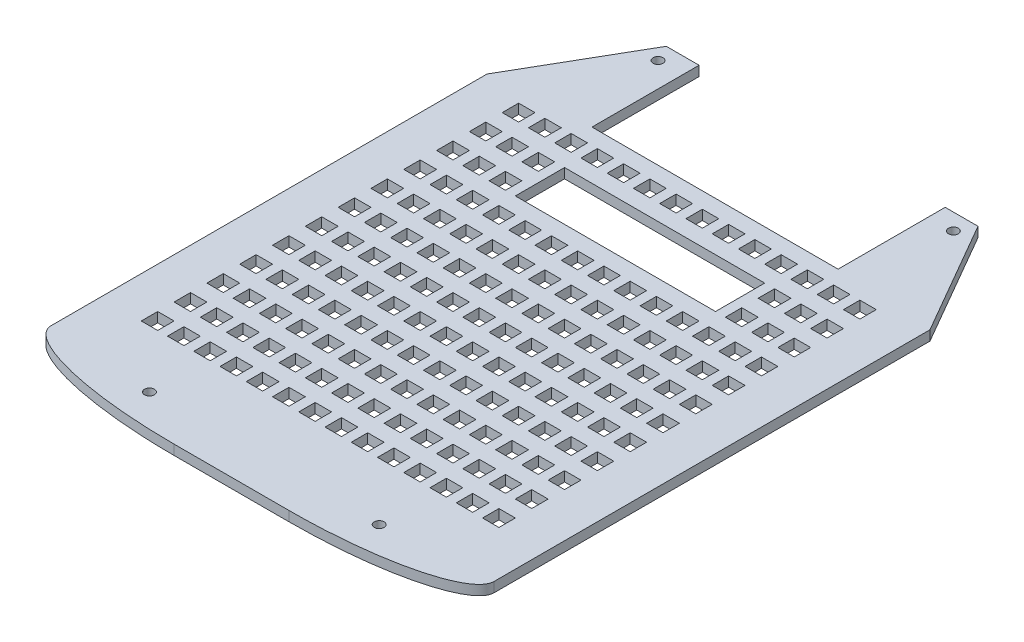
SolidWorks part; units mm, degrees
material "Balsa"
ref_plane "Alzado" through (0, 0, 0) normal (0, 0, 1) x (1, 0, 0)
ref_plane "Planta" through (0, 0, 0) normal (0, 1, 0) x (1, 0, 0)
ref_plane "Vista lateral" through (0, 0, 0) normal (1, 0, 0) x (0, 0, -1)
sketch "Sketch2" plane through (0, 0, 0) normal (0, 1, 0) x (1, 0, 0)
  line L1 (-67.5, 90) -> (67.5, 90)
  line L2 (-67.5, 90) -> (-67.5, -90)
  line L3 (-67.5, -90) -> (67.5, -90)
  line L4 (67.5, 90) -> (67.5, -90)
  line L5 (-67.5, 90) -> (67.5, -90) construction
  line L6 (-67.5, -90) -> (67.5, 90) construction
  point P0 (0, 0)
  dimension "D1" = 135
  dimension "D2" = 180
extrude "Boss-Extrude2" add sketch "Sketch2" along normal blind 3
fillet "Fillet1" radius 12.5 1 edges at (-67.5, 1.5, 90) second distance 50 first distance on face at (-67.5, 1.5, 0)
fillet "Fillet2" radius 12.5 1 edges at (67.5, 1.5, 90) second distance 50 first distance on face at (67.5, 1.5, 0)
chamfer "Chamfer2" distance 20 angle 60 1 edges at (67.5, 1.5, -90) first distance on face at (0, 1.5, -90)
chamfer "Chamfer3" distance 20 angle 60 1 edges at (-67.5, 1.5, -90) first distance on face at (-10, 1.5, -90)
sketch "Sketch3" plane through (0, 3, 0) normal (0, 1, 0) x (1, 0, 0)
  line L0 (0, 90) -> (0, -90) construction
  line L1 (47.5, 90) -> (-47.5, 90) construction
  line L2 (-17.5, -90) -> (17.5, -90) construction
  circle A0 centre (-35, -80) radius 1.5
  circle A1 centre (-45, 85) radius 1.5
  circle A2 centre (35, -80) radius 1.5
  circle A3 centre (45, 85) radius 1.5
  dimension "D1" = 3
  dimension "D3" = 35
  dimension "D2" = 10
  dimension "D4" = 5
  dimension "D5" = 45
extrude "Cut-Extrude1" cut sketch "Sketch3" against normal blind 10
sketch "Sketch4" plane through (0, 3, 0) normal (0, 1, 0) x (1, 0, 0)
  line L1 (-55, 52.5) -> (-50, 52.5)
  line L2 (-55, 52.5) -> (-55, 47.5)
  line L3 (-55, 47.5) -> (-50, 47.5)
  line L4 (-50, 52.5) -> (-50, 47.5)
  line L674 (47.5, 90) -> (-47.5, 90) construction
  line L675 (-67.5, 55.359) -> (-67.5, -77.5) construction
  line L839 (-47, 52.5) -> (-47, 47.5)
  line L840 (-47, 52.5) -> (-42, 52.5)
  line L841 (-42, 52.5) -> (-42, 47.5)
  line L842 (-47, 47.5) -> (-42, 47.5)
  line L843 (-39, 52.5) -> (-39, 47.5)
  line L844 (-39, 52.5) -> (-34, 52.5)
  line L845 (-34, 52.5) -> (-34, 47.5)
  line L846 (-39, 47.5) -> (-34, 47.5)
  line L847 (-31, 52.5) -> (-31, 47.5)
  line L848 (-31, 52.5) -> (-26, 52.5)
  line L849 (-26, 52.5) -> (-26, 47.5)
  line L850 (-31, 47.5) -> (-26, 47.5)
  line L851 (-23, 52.5) -> (-23, 47.5)
  line L852 (-23, 52.5) -> (-18, 52.5)
  line L853 (-18, 52.5) -> (-18, 47.5)
  line L854 (-23, 47.5) -> (-18, 47.5)
  line L855 (-15, 52.5) -> (-15, 47.5)
  line L856 (-15, 52.5) -> (-10, 52.5)
  line L857 (-10, 52.5) -> (-10, 47.5)
  line L858 (-15, 47.5) -> (-10, 47.5)
  line L859 (-7, 52.5) -> (-7, 47.5)
  line L860 (-7, 52.5) -> (-2, 52.5)
  line L861 (-2, 52.5) -> (-2, 47.5)
  line L862 (-7, 47.5) -> (-2, 47.5)
  line L863 (1, 52.5) -> (1, 47.5)
  line L864 (1, 52.5) -> (6, 52.5)
  line L865 (6, 52.5) -> (6, 47.5)
  line L866 (1, 47.5) -> (6, 47.5)
  line L867 (9, 52.5) -> (9, 47.5)
  line L868 (9, 52.5) -> (14, 52.5)
  line L869 (14, 52.5) -> (14, 47.5)
  line L870 (9, 47.5) -> (14, 47.5)
  line L871 (17, 52.5) -> (17, 47.5)
  line L872 (17, 52.5) -> (22, 52.5)
  line L873 (22, 52.5) -> (22, 47.5)
  line L874 (17, 47.5) -> (22, 47.5)
  line L875 (25, 52.5) -> (25, 47.5)
  line L876 (25, 52.5) -> (30, 52.5)
  line L877 (30, 52.5) -> (30, 47.5)
  line L878 (25, 47.5) -> (30, 47.5)
  line L879 (33, 52.5) -> (33, 47.5)
  line L880 (33, 52.5) -> (38, 52.5)
  line L881 (38, 52.5) -> (38, 47.5)
  line L882 (33, 47.5) -> (38, 47.5)
  line L883 (41, 52.5) -> (41, 47.5)
  line L884 (41, 52.5) -> (46, 52.5)
  line L885 (46, 52.5) -> (46, 47.5)
  line L886 (41, 47.5) -> (46, 47.5)
  line L887 (49, 52.5) -> (49, 47.5)
  line L888 (49, 52.5) -> (54, 52.5)
  line L889 (54, 52.5) -> (54, 47.5)
  line L890 (49, 47.5) -> (54, 47.5)
  line L891 (-47, 42.5) -> (-47, 37.5)
  line L892 (-47, 42.5) -> (-42, 42.5)
  line L893 (-42, 42.5) -> (-42, 37.5)
  line L894 (-47, 37.5) -> (-42, 37.5)
  line L895 (-39, 42.5) -> (-39, 37.5)
  line L896 (-39, 42.5) -> (-34, 42.5)
  line L897 (-34, 42.5) -> (-34, 37.5)
  line L898 (-39, 37.5) -> (-34, 37.5)
  line L899 (-31, 42.5) -> (-31, 37.5)
  line L900 (-31, 42.5) -> (-26, 42.5)
  line L901 (-26, 42.5) -> (-26, 37.5)
  line L902 (-31, 37.5) -> (-26, 37.5)
  line L903 (-23, 42.5) -> (-23, 37.5)
  line L904 (-23, 42.5) -> (-18, 42.5)
  line L905 (-18, 42.5) -> (-18, 37.5)
  line L906 (-23, 37.5) -> (-18, 37.5)
  line L907 (-15, 42.5) -> (-15, 37.5)
  line L908 (-15, 42.5) -> (-10, 42.5)
  line L909 (-10, 42.5) -> (-10, 37.5)
  line L910 (-15, 37.5) -> (-10, 37.5)
  line L911 (-7, 42.5) -> (-7, 37.5)
  line L912 (-7, 42.5) -> (-2, 42.5)
  line L913 (-2, 42.5) -> (-2, 37.5)
  line L914 (-7, 37.5) -> (-2, 37.5)
  line L915 (1, 42.5) -> (1, 37.5)
  line L916 (1, 42.5) -> (6, 42.5)
  line L917 (6, 42.5) -> (6, 37.5)
  line L918 (1, 37.5) -> (6, 37.5)
  line L919 (9, 42.5) -> (9, 37.5)
  line L920 (9, 42.5) -> (14, 42.5)
  line L921 (14, 42.5) -> (14, 37.5)
  line L922 (9, 37.5) -> (14, 37.5)
  line L923 (17, 42.5) -> (17, 37.5)
  line L924 (17, 42.5) -> (22, 42.5)
  line L925 (22, 42.5) -> (22, 37.5)
  line L926 (17, 37.5) -> (22, 37.5)
  line L927 (25, 42.5) -> (25, 37.5)
  line L928 (25, 42.5) -> (30, 42.5)
  line L929 (30, 42.5) -> (30, 37.5)
  line L930 (25, 37.5) -> (30, 37.5)
  line L931 (33, 42.5) -> (33, 37.5)
  line L932 (33, 42.5) -> (38, 42.5)
  line L933 (38, 42.5) -> (38, 37.5)
  line L934 (33, 37.5) -> (38, 37.5)
  line L935 (41, 42.5) -> (41, 37.5)
  line L936 (41, 42.5) -> (46, 42.5)
  line L937 (46, 42.5) -> (46, 37.5)
  line L938 (41, 37.5) -> (46, 37.5)
  line L939 (49, 42.5) -> (49, 37.5)
  line L940 (49, 42.5) -> (54, 42.5)
  line L941 (54, 42.5) -> (54, 37.5)
  line L942 (49, 37.5) -> (54, 37.5)
  line L943 (-47, 32.5) -> (-47, 27.5)
  line L944 (-47, 32.5) -> (-42, 32.5)
  line L945 (-42, 32.5) -> (-42, 27.5)
  line L946 (-47, 27.5) -> (-42, 27.5)
  line L947 (-39, 32.5) -> (-39, 27.5)
  line L948 (-39, 32.5) -> (-34, 32.5)
  line L949 (-34, 32.5) -> (-34, 27.5)
  line L950 (-39, 27.5) -> (-34, 27.5)
  line L951 (-31, 32.5) -> (-31, 27.5)
  line L952 (-31, 32.5) -> (-26, 32.5)
  line L953 (-26, 32.5) -> (-26, 27.5)
  line L954 (-31, 27.5) -> (-26, 27.5)
  line L955 (-23, 32.5) -> (-23, 27.5)
  line L956 (-23, 32.5) -> (-18, 32.5)
  line L957 (-18, 32.5) -> (-18, 27.5)
  line L958 (-23, 27.5) -> (-18, 27.5)
  line L959 (-15, 32.5) -> (-15, 27.5)
  line L960 (-15, 32.5) -> (-10, 32.5)
  line L961 (-10, 32.5) -> (-10, 27.5)
  line L962 (-15, 27.5) -> (-10, 27.5)
  line L963 (-7, 32.5) -> (-7, 27.5)
  line L964 (-7, 32.5) -> (-2, 32.5)
  line L965 (-2, 32.5) -> (-2, 27.5)
  line L966 (-7, 27.5) -> (-2, 27.5)
  line L967 (1, 32.5) -> (1, 27.5)
  line L968 (1, 32.5) -> (6, 32.5)
  line L969 (6, 32.5) -> (6, 27.5)
  line L970 (1, 27.5) -> (6, 27.5)
  line L971 (9, 32.5) -> (9, 27.5)
  line L972 (9, 32.5) -> (14, 32.5)
  line L973 (14, 32.5) -> (14, 27.5)
  line L974 (9, 27.5) -> (14, 27.5)
  line L975 (17, 32.5) -> (17, 27.5)
  line L976 (17, 32.5) -> (22, 32.5)
  line L977 (22, 32.5) -> (22, 27.5)
  line L978 (17, 27.5) -> (22, 27.5)
  line L979 (25, 32.5) -> (25, 27.5)
  line L980 (25, 32.5) -> (30, 32.5)
  line L981 (30, 32.5) -> (30, 27.5)
  line L982 (25, 27.5) -> (30, 27.5)
  line L983 (33, 32.5) -> (33, 27.5)
  line L984 (33, 32.5) -> (38, 32.5)
  line L985 (38, 32.5) -> (38, 27.5)
  line L986 (33, 27.5) -> (38, 27.5)
  line L987 (41, 32.5) -> (41, 27.5)
  line L988 (41, 32.5) -> (46, 32.5)
  line L989 (46, 32.5) -> (46, 27.5)
  line L990 (41, 27.5) -> (46, 27.5)
  line L991 (49, 32.5) -> (49, 27.5)
  line L992 (49, 32.5) -> (54, 32.5)
  line L993 (54, 32.5) -> (54, 27.5)
  line L994 (49, 27.5) -> (54, 27.5)
  line L995 (-47, 22.5) -> (-47, 17.5)
  line L996 (-47, 22.5) -> (-42, 22.5)
  line L997 (-42, 22.5) -> (-42, 17.5)
  line L998 (-47, 17.5) -> (-42, 17.5)
  line L999 (-39, 22.5) -> (-39, 17.5)
  line L1000 (-39, 22.5) -> (-34, 22.5)
  line L1001 (-34, 22.5) -> (-34, 17.5)
  line L1002 (-39, 17.5) -> (-34, 17.5)
  line L1003 (-31, 22.5) -> (-31, 17.5)
  line L1004 (-31, 22.5) -> (-26, 22.5)
  line L1005 (-26, 22.5) -> (-26, 17.5)
  line L1006 (-31, 17.5) -> (-26, 17.5)
  line L1007 (-23, 22.5) -> (-23, 17.5)
  line L1008 (-23, 22.5) -> (-18, 22.5)
  line L1009 (-18, 22.5) -> (-18, 17.5)
  line L1010 (-23, 17.5) -> (-18, 17.5)
  line L1011 (-15, 22.5) -> (-15, 17.5)
  line L1012 (-15, 22.5) -> (-10, 22.5)
  line L1013 (-10, 22.5) -> (-10, 17.5)
  line L1014 (-15, 17.5) -> (-10, 17.5)
  line L1015 (-7, 22.5) -> (-7, 17.5)
  line L1016 (-7, 22.5) -> (-2, 22.5)
  line L1017 (-2, 22.5) -> (-2, 17.5)
  line L1018 (-7, 17.5) -> (-2, 17.5)
  line L1019 (1, 22.5) -> (1, 17.5)
  line L1020 (1, 22.5) -> (6, 22.5)
  line L1021 (6, 22.5) -> (6, 17.5)
  line L1022 (1, 17.5) -> (6, 17.5)
  line L1023 (9, 22.5) -> (9, 17.5)
  line L1024 (9, 22.5) -> (14, 22.5)
  line L1025 (14, 22.5) -> (14, 17.5)
  line L1026 (9, 17.5) -> (14, 17.5)
  line L1027 (17, 22.5) -> (17, 17.5)
  line L1028 (17, 22.5) -> (22, 22.5)
  line L1029 (22, 22.5) -> (22, 17.5)
  line L1030 (17, 17.5) -> (22, 17.5)
  line L1031 (25, 22.5) -> (25, 17.5)
  line L1032 (25, 22.5) -> (30, 22.5)
  line L1033 (30, 22.5) -> (30, 17.5)
  line L1034 (25, 17.5) -> (30, 17.5)
  line L1035 (33, 22.5) -> (33, 17.5)
  line L1036 (33, 22.5) -> (38, 22.5)
  line L1037 (38, 22.5) -> (38, 17.5)
  line L1038 (33, 17.5) -> (38, 17.5)
  line L1039 (41, 22.5) -> (41, 17.5)
  line L1040 (41, 22.5) -> (46, 22.5)
  line L1041 (46, 22.5) -> (46, 17.5)
  line L1042 (41, 17.5) -> (46, 17.5)
  line L1043 (49, 22.5) -> (49, 17.5)
  line L1044 (49, 22.5) -> (54, 22.5)
  line L1045 (54, 22.5) -> (54, 17.5)
  line L1046 (49, 17.5) -> (54, 17.5)
  line L1047 (-47, 12.5) -> (-47, 7.5)
  line L1048 (-47, 12.5) -> (-42, 12.5)
  line L1049 (-42, 12.5) -> (-42, 7.5)
  line L1050 (-47, 7.5) -> (-42, 7.5)
  line L1051 (-39, 12.5) -> (-39, 7.5)
  line L1052 (-39, 12.5) -> (-34, 12.5)
  line L1053 (-34, 12.5) -> (-34, 7.5)
  line L1054 (-39, 7.5) -> (-34, 7.5)
  line L1055 (-31, 12.5) -> (-31, 7.5)
  line L1056 (-31, 12.5) -> (-26, 12.5)
  line L1057 (-26, 12.5) -> (-26, 7.5)
  line L1058 (-31, 7.5) -> (-26, 7.5)
  line L1059 (-23, 12.5) -> (-23, 7.5)
  line L1060 (-23, 12.5) -> (-18, 12.5)
  line L1061 (-18, 12.5) -> (-18, 7.5)
  line L1062 (-23, 7.5) -> (-18, 7.5)
  line L1063 (-15, 12.5) -> (-15, 7.5)
  line L1064 (-15, 12.5) -> (-10, 12.5)
  line L1065 (-10, 12.5) -> (-10, 7.5)
  line L1066 (-15, 7.5) -> (-10, 7.5)
  line L1067 (-7, 12.5) -> (-7, 7.5)
  line L1068 (-7, 12.5) -> (-2, 12.5)
  line L1069 (-2, 12.5) -> (-2, 7.5)
  line L1070 (-7, 7.5) -> (-2, 7.5)
  line L1071 (1, 12.5) -> (1, 7.5)
  line L1072 (1, 12.5) -> (6, 12.5)
  line L1073 (6, 12.5) -> (6, 7.5)
  line L1074 (1, 7.5) -> (6, 7.5)
  line L1075 (9, 12.5) -> (9, 7.5)
  line L1076 (9, 12.5) -> (14, 12.5)
  line L1077 (14, 12.5) -> (14, 7.5)
  line L1078 (9, 7.5) -> (14, 7.5)
  line L1079 (17, 12.5) -> (17, 7.5)
  line L1080 (17, 12.5) -> (22, 12.5)
  line L1081 (22, 12.5) -> (22, 7.5)
  line L1082 (17, 7.5) -> (22, 7.5)
  line L1083 (25, 12.5) -> (25, 7.5)
  line L1084 (25, 12.5) -> (30, 12.5)
  line L1085 (30, 12.5) -> (30, 7.5)
  line L1086 (25, 7.5) -> (30, 7.5)
  line L1087 (33, 12.5) -> (33, 7.5)
  line L1088 (33, 12.5) -> (38, 12.5)
  line L1089 (38, 12.5) -> (38, 7.5)
  line L1090 (33, 7.5) -> (38, 7.5)
  line L1091 (41, 12.5) -> (41, 7.5)
  line L1092 (41, 12.5) -> (46, 12.5)
  line L1093 (46, 12.5) -> (46, 7.5)
  line L1094 (41, 7.5) -> (46, 7.5)
  line L1095 (49, 12.5) -> (49, 7.5)
  line L1096 (49, 12.5) -> (54, 12.5)
  line L1097 (54, 12.5) -> (54, 7.5)
  line L1098 (49, 7.5) -> (54, 7.5)
  line L1099 (-47, 2.5) -> (-47, -2.5)
  line L1100 (-47, 2.5) -> (-42, 2.5)
  line L1101 (-42, 2.5) -> (-42, -2.5)
  line L1102 (-47, -2.5) -> (-42, -2.5)
  line L1103 (-39, 2.5) -> (-39, -2.5)
  line L1104 (-39, 2.5) -> (-34, 2.5)
  line L1105 (-34, 2.5) -> (-34, -2.5)
  line L1106 (-39, -2.5) -> (-34, -2.5)
  line L1107 (-31, 2.5) -> (-31, -2.5)
  line L1108 (-31, 2.5) -> (-26, 2.5)
  line L1109 (-26, 2.5) -> (-26, -2.5)
  line L1110 (-31, -2.5) -> (-26, -2.5)
  line L1111 (-23, 2.5) -> (-23, -2.5)
  line L1112 (-23, 2.5) -> (-18, 2.5)
  line L1113 (-18, 2.5) -> (-18, -2.5)
  line L1114 (-23, -2.5) -> (-18, -2.5)
  line L1115 (-15, 2.5) -> (-15, -2.5)
  line L1116 (-15, 2.5) -> (-10, 2.5)
  line L1117 (-10, 2.5) -> (-10, -2.5)
  line L1118 (-15, -2.5) -> (-10, -2.5)
  line L1119 (-7, 2.5) -> (-7, -2.5)
  line L1120 (-7, 2.5) -> (-2, 2.5)
  line L1121 (-2, 2.5) -> (-2, -2.5)
  line L1122 (-7, -2.5) -> (-2, -2.5)
  line L1123 (1, 2.5) -> (1, -2.5)
  line L1124 (1, 2.5) -> (6, 2.5)
  line L1125 (6, 2.5) -> (6, -2.5)
  line L1126 (1, -2.5) -> (6, -2.5)
  line L1127 (9, 2.5) -> (9, -2.5)
  line L1128 (9, 2.5) -> (14, 2.5)
  line L1129 (14, 2.5) -> (14, -2.5)
  line L1130 (9, -2.5) -> (14, -2.5)
  line L1131 (17, 2.5) -> (17, -2.5)
  line L1132 (17, 2.5) -> (22, 2.5)
  line L1133 (22, 2.5) -> (22, -2.5)
  line L1134 (17, -2.5) -> (22, -2.5)
  line L1135 (25, 2.5) -> (25, -2.5)
  line L1136 (25, 2.5) -> (30, 2.5)
  line L1137 (30, 2.5) -> (30, -2.5)
  line L1138 (25, -2.5) -> (30, -2.5)
  line L1139 (33, 2.5) -> (33, -2.5)
  line L1140 (33, 2.5) -> (38, 2.5)
  line L1141 (38, 2.5) -> (38, -2.5)
  line L1142 (33, -2.5) -> (38, -2.5)
  line L1143 (41, 2.5) -> (41, -2.5)
  line L1144 (41, 2.5) -> (46, 2.5)
  line L1145 (46, 2.5) -> (46, -2.5)
  line L1146 (41, -2.5) -> (46, -2.5)
  line L1147 (49, 2.5) -> (49, -2.5)
  line L1148 (49, 2.5) -> (54, 2.5)
  line L1149 (54, 2.5) -> (54, -2.5)
  line L1150 (49, -2.5) -> (54, -2.5)
  line L1151 (-47, -7.5) -> (-47, -12.5)
  line L1152 (-47, -7.5) -> (-42, -7.5)
  line L1153 (-42, -7.5) -> (-42, -12.5)
  line L1154 (-47, -12.5) -> (-42, -12.5)
  line L1155 (-39, -7.5) -> (-39, -12.5)
  line L1156 (-39, -7.5) -> (-34, -7.5)
  line L1157 (-34, -7.5) -> (-34, -12.5)
  line L1158 (-39, -12.5) -> (-34, -12.5)
  line L1159 (-31, -7.5) -> (-31, -12.5)
  line L1160 (-31, -7.5) -> (-26, -7.5)
  line L1161 (-26, -7.5) -> (-26, -12.5)
  line L1162 (-31, -12.5) -> (-26, -12.5)
  line L1163 (-23, -7.5) -> (-23, -12.5)
  line L1164 (-23, -7.5) -> (-18, -7.5)
  line L1165 (-18, -7.5) -> (-18, -12.5)
  line L1166 (-23, -12.5) -> (-18, -12.5)
  line L1167 (-15, -7.5) -> (-15, -12.5)
  line L1168 (-15, -7.5) -> (-10, -7.5)
  line L1169 (-10, -7.5) -> (-10, -12.5)
  line L1170 (-15, -12.5) -> (-10, -12.5)
  line L1171 (-7, -7.5) -> (-7, -12.5)
  line L1172 (-7, -7.5) -> (-2, -7.5)
  line L1173 (-2, -7.5) -> (-2, -12.5)
  line L1174 (-7, -12.5) -> (-2, -12.5)
  line L1175 (1, -7.5) -> (1, -12.5)
  line L1176 (1, -7.5) -> (6, -7.5)
  line L1177 (6, -7.5) -> (6, -12.5)
  line L1178 (1, -12.5) -> (6, -12.5)
  line L1179 (9, -7.5) -> (9, -12.5)
  line L1180 (9, -7.5) -> (14, -7.5)
  line L1181 (14, -7.5) -> (14, -12.5)
  line L1182 (9, -12.5) -> (14, -12.5)
  line L1183 (17, -7.5) -> (17, -12.5)
  line L1184 (17, -7.5) -> (22, -7.5)
  line L1185 (22, -7.5) -> (22, -12.5)
  line L1186 (17, -12.5) -> (22, -12.5)
  line L1187 (25, -7.5) -> (25, -12.5)
  line L1188 (25, -7.5) -> (30, -7.5)
  line L1189 (30, -7.5) -> (30, -12.5)
  line L1190 (25, -12.5) -> (30, -12.5)
  line L1191 (33, -7.5) -> (33, -12.5)
  line L1192 (33, -7.5) -> (38, -7.5)
  line L1193 (38, -7.5) -> (38, -12.5)
  line L1194 (33, -12.5) -> (38, -12.5)
  line L1195 (41, -7.5) -> (41, -12.5)
  line L1196 (41, -7.5) -> (46, -7.5)
  line L1197 (46, -7.5) -> (46, -12.5)
  line L1198 (41, -12.5) -> (46, -12.5)
  line L1199 (49, -7.5) -> (49, -12.5)
  line L1200 (49, -7.5) -> (54, -7.5)
  line L1201 (54, -7.5) -> (54, -12.5)
  line L1202 (49, -12.5) -> (54, -12.5)
  line L1203 (-47, -17.5) -> (-47, -22.5)
  line L1204 (-47, -17.5) -> (-42, -17.5)
  line L1205 (-42, -17.5) -> (-42, -22.5)
  line L1206 (-47, -22.5) -> (-42, -22.5)
  line L1207 (-39, -17.5) -> (-39, -22.5)
  line L1208 (-39, -17.5) -> (-34, -17.5)
  line L1209 (-34, -17.5) -> (-34, -22.5)
  line L1210 (-39, -22.5) -> (-34, -22.5)
  line L1211 (-31, -17.5) -> (-31, -22.5)
  line L1212 (-31, -17.5) -> (-26, -17.5)
  line L1213 (-26, -17.5) -> (-26, -22.5)
  line L1214 (-31, -22.5) -> (-26, -22.5)
  line L1215 (-23, -17.5) -> (-23, -22.5)
  line L1216 (-23, -17.5) -> (-18, -17.5)
  line L1217 (-18, -17.5) -> (-18, -22.5)
  line L1218 (-23, -22.5) -> (-18, -22.5)
  line L1219 (-15, -17.5) -> (-15, -22.5)
  line L1220 (-15, -17.5) -> (-10, -17.5)
  line L1221 (-10, -17.5) -> (-10, -22.5)
  line L1222 (-15, -22.5) -> (-10, -22.5)
  line L1223 (-7, -17.5) -> (-7, -22.5)
  line L1224 (-7, -17.5) -> (-2, -17.5)
  line L1225 (-2, -17.5) -> (-2, -22.5)
  line L1226 (-7, -22.5) -> (-2, -22.5)
  line L1227 (1, -17.5) -> (1, -22.5)
  line L1228 (1, -17.5) -> (6, -17.5)
  line L1229 (6, -17.5) -> (6, -22.5)
  line L1230 (1, -22.5) -> (6, -22.5)
  line L1231 (9, -17.5) -> (9, -22.5)
  line L1232 (9, -17.5) -> (14, -17.5)
  line L1233 (14, -17.5) -> (14, -22.5)
  line L1234 (9, -22.5) -> (14, -22.5)
  line L1235 (17, -17.5) -> (17, -22.5)
  line L1236 (17, -17.5) -> (22, -17.5)
  line L1237 (22, -17.5) -> (22, -22.5)
  line L1238 (17, -22.5) -> (22, -22.5)
  line L1239 (25, -17.5) -> (25, -22.5)
  line L1240 (25, -17.5) -> (30, -17.5)
  line L1241 (30, -17.5) -> (30, -22.5)
  line L1242 (25, -22.5) -> (30, -22.5)
  line L1243 (33, -17.5) -> (33, -22.5)
  line L1244 (33, -17.5) -> (38, -17.5)
  line L1245 (38, -17.5) -> (38, -22.5)
  line L1246 (33, -22.5) -> (38, -22.5)
  line L1247 (41, -17.5) -> (41, -22.5)
  line L1248 (41, -17.5) -> (46, -17.5)
  line L1249 (46, -17.5) -> (46, -22.5)
  line L1250 (41, -22.5) -> (46, -22.5)
  line L1251 (49, -17.5) -> (49, -22.5)
  line L1252 (49, -17.5) -> (54, -17.5)
  line L1253 (54, -17.5) -> (54, -22.5)
  line L1254 (49, -22.5) -> (54, -22.5)
  line L1255 (-47, -27.5) -> (-47, -32.5)
  line L1256 (-47, -27.5) -> (-42, -27.5)
  line L1257 (-42, -27.5) -> (-42, -32.5)
  line L1258 (-47, -32.5) -> (-42, -32.5)
  line L1259 (-39, -27.5) -> (-39, -32.5)
  line L1260 (-39, -27.5) -> (-34, -27.5)
  line L1261 (-34, -27.5) -> (-34, -32.5)
  line L1262 (-39, -32.5) -> (-34, -32.5)
  line L1263 (-31, -27.5) -> (-31, -32.5)
  line L1264 (-31, -27.5) -> (-26, -27.5)
  line L1265 (-26, -27.5) -> (-26, -32.5)
  line L1266 (-31, -32.5) -> (-26, -32.5)
  line L1267 (-23, -27.5) -> (-23, -32.5)
  line L1268 (-23, -27.5) -> (-18, -27.5)
  line L1269 (-18, -27.5) -> (-18, -32.5)
  line L1270 (-23, -32.5) -> (-18, -32.5)
  line L1271 (-15, -27.5) -> (-15, -32.5)
  line L1272 (-15, -27.5) -> (-10, -27.5)
  line L1273 (-10, -27.5) -> (-10, -32.5)
  line L1274 (-15, -32.5) -> (-10, -32.5)
  line L1275 (-7, -27.5) -> (-7, -32.5)
  line L1276 (-7, -27.5) -> (-2, -27.5)
  line L1277 (-2, -27.5) -> (-2, -32.5)
  line L1278 (-7, -32.5) -> (-2, -32.5)
  line L1279 (1, -27.5) -> (1, -32.5)
  line L1280 (1, -27.5) -> (6, -27.5)
  line L1281 (6, -27.5) -> (6, -32.5)
  line L1282 (1, -32.5) -> (6, -32.5)
  line L1283 (9, -27.5) -> (9, -32.5)
  line L1284 (9, -27.5) -> (14, -27.5)
  line L1285 (14, -27.5) -> (14, -32.5)
  line L1286 (9, -32.5) -> (14, -32.5)
  line L1287 (17, -27.5) -> (17, -32.5)
  line L1288 (17, -27.5) -> (22, -27.5)
  line L1289 (22, -27.5) -> (22, -32.5)
  line L1290 (17, -32.5) -> (22, -32.5)
  line L1291 (25, -27.5) -> (25, -32.5)
  line L1292 (25, -27.5) -> (30, -27.5)
  line L1293 (30, -27.5) -> (30, -32.5)
  line L1294 (25, -32.5) -> (30, -32.5)
  line L1295 (33, -27.5) -> (33, -32.5)
  line L1296 (33, -27.5) -> (38, -27.5)
  line L1297 (38, -27.5) -> (38, -32.5)
  line L1298 (33, -32.5) -> (38, -32.5)
  line L1299 (41, -27.5) -> (41, -32.5)
  line L1300 (41, -27.5) -> (46, -27.5)
  line L1301 (46, -27.5) -> (46, -32.5)
  line L1302 (41, -32.5) -> (46, -32.5)
  line L1303 (49, -27.5) -> (49, -32.5)
  line L1304 (49, -27.5) -> (54, -27.5)
  line L1305 (54, -27.5) -> (54, -32.5)
  line L1306 (49, -32.5) -> (54, -32.5)
  line L1307 (-47, -37.5) -> (-47, -42.5)
  line L1308 (-47, -37.5) -> (-42, -37.5)
  line L1309 (-42, -37.5) -> (-42, -42.5)
  line L1310 (-47, -42.5) -> (-42, -42.5)
  line L1311 (-39, -37.5) -> (-39, -42.5)
  line L1312 (-39, -37.5) -> (-34, -37.5)
  line L1313 (-34, -37.5) -> (-34, -42.5)
  line L1314 (-39, -42.5) -> (-34, -42.5)
  line L1315 (-31, -37.5) -> (-31, -42.5)
  line L1316 (-31, -37.5) -> (-26, -37.5)
  line L1317 (-26, -37.5) -> (-26, -42.5)
  line L1318 (-31, -42.5) -> (-26, -42.5)
  line L1319 (-23, -37.5) -> (-23, -42.5)
  line L1320 (-23, -37.5) -> (-18, -37.5)
  line L1321 (-18, -37.5) -> (-18, -42.5)
  line L1322 (-23, -42.5) -> (-18, -42.5)
  line L1323 (-15, -37.5) -> (-15, -42.5)
  line L1324 (-15, -37.5) -> (-10, -37.5)
  line L1325 (-10, -37.5) -> (-10, -42.5)
  line L1326 (-15, -42.5) -> (-10, -42.5)
  line L1327 (-7, -37.5) -> (-7, -42.5)
  line L1328 (-7, -37.5) -> (-2, -37.5)
  line L1329 (-2, -37.5) -> (-2, -42.5)
  line L1330 (-7, -42.5) -> (-2, -42.5)
  line L1331 (1, -37.5) -> (1, -42.5)
  line L1332 (1, -37.5) -> (6, -37.5)
  line L1333 (6, -37.5) -> (6, -42.5)
  line L1334 (1, -42.5) -> (6, -42.5)
  line L1335 (9, -37.5) -> (9, -42.5)
  line L1336 (9, -37.5) -> (14, -37.5)
  line L1337 (14, -37.5) -> (14, -42.5)
  line L1338 (9, -42.5) -> (14, -42.5)
  line L1339 (17, -37.5) -> (17, -42.5)
  line L1340 (17, -37.5) -> (22, -37.5)
  line L1341 (22, -37.5) -> (22, -42.5)
  line L1342 (17, -42.5) -> (22, -42.5)
  line L1343 (25, -37.5) -> (25, -42.5)
  line L1344 (25, -37.5) -> (30, -37.5)
  line L1345 (30, -37.5) -> (30, -42.5)
  line L1346 (25, -42.5) -> (30, -42.5)
  line L1347 (33, -37.5) -> (33, -42.5)
  line L1348 (33, -37.5) -> (38, -37.5)
  line L1349 (38, -37.5) -> (38, -42.5)
  line L1350 (33, -42.5) -> (38, -42.5)
  line L1351 (41, -37.5) -> (41, -42.5)
  line L1352 (41, -37.5) -> (46, -37.5)
  line L1353 (46, -37.5) -> (46, -42.5)
  line L1354 (41, -42.5) -> (46, -42.5)
  line L1355 (49, -37.5) -> (49, -42.5)
  line L1356 (49, -37.5) -> (54, -37.5)
  line L1357 (54, -37.5) -> (54, -42.5)
  line L1358 (49, -42.5) -> (54, -42.5)
  line L1359 (-47, -47.5) -> (-47, -52.5)
  line L1360 (-47, -47.5) -> (-42, -47.5)
  line L1361 (-42, -47.5) -> (-42, -52.5)
  line L1362 (-47, -52.5) -> (-42, -52.5)
  line L1363 (-39, -47.5) -> (-39, -52.5)
  line L1364 (-39, -47.5) -> (-34, -47.5)
  line L1365 (-34, -47.5) -> (-34, -52.5)
  line L1366 (-39, -52.5) -> (-34, -52.5)
  line L1367 (-31, -47.5) -> (-31, -52.5)
  line L1368 (-31, -47.5) -> (-26, -47.5)
  line L1369 (-26, -47.5) -> (-26, -52.5)
  line L1370 (-31, -52.5) -> (-26, -52.5)
  line L1371 (-23, -47.5) -> (-23, -52.5)
  line L1372 (-23, -47.5) -> (-18, -47.5)
  line L1373 (-18, -47.5) -> (-18, -52.5)
  line L1374 (-23, -52.5) -> (-18, -52.5)
  line L1375 (-15, -47.5) -> (-15, -52.5)
  line L1376 (-15, -47.5) -> (-10, -47.5)
  line L1377 (-10, -47.5) -> (-10, -52.5)
  line L1378 (-15, -52.5) -> (-10, -52.5)
  line L1379 (-7, -47.5) -> (-7, -52.5)
  line L1380 (-7, -47.5) -> (-2, -47.5)
  line L1381 (-2, -47.5) -> (-2, -52.5)
  line L1382 (-7, -52.5) -> (-2, -52.5)
  line L1383 (1, -47.5) -> (1, -52.5)
  line L1384 (1, -47.5) -> (6, -47.5)
  line L1385 (6, -47.5) -> (6, -52.5)
  line L1386 (1, -52.5) -> (6, -52.5)
  line L1387 (9, -47.5) -> (9, -52.5)
  line L1388 (9, -47.5) -> (14, -47.5)
  line L1389 (14, -47.5) -> (14, -52.5)
  line L1390 (9, -52.5) -> (14, -52.5)
  line L1391 (17, -47.5) -> (17, -52.5)
  line L1392 (17, -47.5) -> (22, -47.5)
  line L1393 (22, -47.5) -> (22, -52.5)
  line L1394 (17, -52.5) -> (22, -52.5)
  line L1395 (25, -47.5) -> (25, -52.5)
  line L1396 (25, -47.5) -> (30, -47.5)
  line L1397 (30, -47.5) -> (30, -52.5)
  line L1398 (25, -52.5) -> (30, -52.5)
  line L1399 (33, -47.5) -> (33, -52.5)
  line L1400 (33, -47.5) -> (38, -47.5)
  line L1401 (38, -47.5) -> (38, -52.5)
  line L1402 (33, -52.5) -> (38, -52.5)
  line L1403 (41, -47.5) -> (41, -52.5)
  line L1404 (41, -47.5) -> (46, -47.5)
  line L1405 (46, -47.5) -> (46, -52.5)
  line L1406 (41, -52.5) -> (46, -52.5)
  line L1407 (49, -47.5) -> (49, -52.5)
  line L1408 (49, -47.5) -> (54, -47.5)
  line L1409 (54, -47.5) -> (54, -52.5)
  line L1410 (49, -52.5) -> (54, -52.5)
  line L1411 (-47, -57.5) -> (-47, -62.5)
  line L1412 (-47, -57.5) -> (-42, -57.5)
  line L1413 (-42, -57.5) -> (-42, -62.5)
  line L1414 (-47, -62.5) -> (-42, -62.5)
  line L1415 (-39, -57.5) -> (-39, -62.5)
  line L1416 (-39, -57.5) -> (-34, -57.5)
  line L1417 (-34, -57.5) -> (-34, -62.5)
  line L1418 (-39, -62.5) -> (-34, -62.5)
  line L1419 (-31, -57.5) -> (-31, -62.5)
  line L1420 (-31, -57.5) -> (-26, -57.5)
  line L1421 (-26, -57.5) -> (-26, -62.5)
  line L1422 (-31, -62.5) -> (-26, -62.5)
  line L1423 (-23, -57.5) -> (-23, -62.5)
  line L1424 (-23, -57.5) -> (-18, -57.5)
  line L1425 (-18, -57.5) -> (-18, -62.5)
  line L1426 (-23, -62.5) -> (-18, -62.5)
  line L1427 (-15, -57.5) -> (-15, -62.5)
  line L1428 (-15, -57.5) -> (-10, -57.5)
  line L1429 (-10, -57.5) -> (-10, -62.5)
  line L1430 (-15, -62.5) -> (-10, -62.5)
  line L1431 (-7, -57.5) -> (-7, -62.5)
  line L1432 (-7, -57.5) -> (-2, -57.5)
  line L1433 (-2, -57.5) -> (-2, -62.5)
  line L1434 (-7, -62.5) -> (-2, -62.5)
  line L1435 (1, -57.5) -> (1, -62.5)
  line L1436 (1, -57.5) -> (6, -57.5)
  line L1437 (6, -57.5) -> (6, -62.5)
  line L1438 (1, -62.5) -> (6, -62.5)
  line L1439 (9, -57.5) -> (9, -62.5)
  line L1440 (9, -57.5) -> (14, -57.5)
  line L1441 (14, -57.5) -> (14, -62.5)
  line L1442 (9, -62.5) -> (14, -62.5)
  line L1443 (17, -57.5) -> (17, -62.5)
  line L1444 (17, -57.5) -> (22, -57.5)
  line L1445 (22, -57.5) -> (22, -62.5)
  line L1446 (17, -62.5) -> (22, -62.5)
  line L1447 (25, -57.5) -> (25, -62.5)
  line L1448 (25, -57.5) -> (30, -57.5)
  line L1449 (30, -57.5) -> (30, -62.5)
  line L1450 (25, -62.5) -> (30, -62.5)
  line L1451 (33, -57.5) -> (33, -62.5)
  line L1452 (33, -57.5) -> (38, -57.5)
  line L1453 (38, -57.5) -> (38, -62.5)
  line L1454 (33, -62.5) -> (38, -62.5)
  line L1455 (41, -57.5) -> (41, -62.5)
  line L1456 (41, -57.5) -> (46, -57.5)
  line L1457 (46, -57.5) -> (46, -62.5)
  line L1458 (41, -62.5) -> (46, -62.5)
  line L1459 (49, -57.5) -> (49, -62.5)
  line L1460 (49, -57.5) -> (54, -57.5)
  line L1461 (54, -57.5) -> (54, -62.5)
  line L1462 (49, -62.5) -> (54, -62.5)
  line L1463 (-55, 42.5) -> (-55, 37.5)
  line L1464 (-55, 42.5) -> (-50, 42.5)
  line L1465 (-50, 42.5) -> (-50, 37.5)
  line L1466 (-55, 37.5) -> (-50, 37.5)
  line L1467 (-55, 32.5) -> (-55, 27.5)
  line L1468 (-55, 32.5) -> (-50, 32.5)
  line L1469 (-50, 32.5) -> (-50, 27.5)
  line L1470 (-55, 27.5) -> (-50, 27.5)
  line L1471 (-55, 22.5) -> (-55, 17.5)
  line L1472 (-55, 22.5) -> (-50, 22.5)
  line L1473 (-50, 22.5) -> (-50, 17.5)
  line L1474 (-55, 17.5) -> (-50, 17.5)
  line L1475 (-55, 12.5) -> (-55, 7.5)
  line L1476 (-55, 12.5) -> (-50, 12.5)
  line L1477 (-50, 12.5) -> (-50, 7.5)
  line L1478 (-55, 7.5) -> (-50, 7.5)
  line L1479 (-55, 2.5) -> (-55, -2.5)
  line L1480 (-55, 2.5) -> (-50, 2.5)
  line L1481 (-50, 2.5) -> (-50, -2.5)
  line L1482 (-55, -2.5) -> (-50, -2.5)
  line L1483 (-55, -7.5) -> (-55, -12.5)
  line L1484 (-55, -7.5) -> (-50, -7.5)
  line L1485 (-50, -7.5) -> (-50, -12.5)
  line L1486 (-55, -12.5) -> (-50, -12.5)
  line L1487 (-55, -17.5) -> (-55, -22.5)
  line L1488 (-55, -17.5) -> (-50, -17.5)
  line L1489 (-50, -17.5) -> (-50, -22.5)
  line L1490 (-55, -22.5) -> (-50, -22.5)
  line L1491 (-55, -27.5) -> (-55, -32.5)
  line L1492 (-55, -27.5) -> (-50, -27.5)
  line L1493 (-50, -27.5) -> (-50, -32.5)
  line L1494 (-55, -32.5) -> (-50, -32.5)
  line L1495 (-55, -37.5) -> (-55, -42.5)
  line L1496 (-55, -37.5) -> (-50, -37.5)
  line L1497 (-50, -37.5) -> (-50, -42.5)
  line L1498 (-55, -42.5) -> (-50, -42.5)
  line L1499 (-55, -47.5) -> (-55, -52.5)
  line L1500 (-55, -47.5) -> (-50, -47.5)
  line L1501 (-50, -47.5) -> (-50, -52.5)
  line L1502 (-55, -52.5) -> (-50, -52.5)
  line L1503 (-55, -57.5) -> (-55, -62.5)
  line L1504 (-55, -57.5) -> (-50, -57.5)
  line L1505 (-50, -57.5) -> (-50, -62.5)
  line L1506 (-55, -62.5) -> (-50, -62.5)
  point P4 (-52.5, 52.5)
  point P9 (-55, 50)
  dimension "D1" = 5
  dimension "D2" = 5
  dimension "D3" = 15
  dimension "D4" = 40
  dimension "D5" = 14
  dimension "D6" = 12
extrude "Cut-Extrude2" cut sketch "Sketch4" against normal blind 10
sketch "Sketch5" plane through (0, 3, 0) normal (0, 1, 0) x (1, 0, 0)
  line L9 (-31, 27.5) -> (30, 27.5)
  line L10 (-31, 27.5) -> (-31, 42.5)
  line L11 (-31, 42.5) -> (30, 42.5)
  line L12 (30, 27.5) -> (30, 42.5)
extrude "Cut-Extrude3" cut sketch "Sketch5" against normal through all
sketch "Sketch6" plane through (0, 3, 0) normal (0, 1, 0) x (1, 0, 0)
  line L0 (47.5, 90) -> (-47.5, 90) construction
  line L1 (-37.5, 90) -> (37.5, 90)
  line L2 (-37.5, 90) -> (-37.5, 57.36)
  line L3 (-37.5, 57.36) -> (37.5, 57.36)
  line L4 (37.5, 90) -> (37.5, 57.36)
  line L5 (0, -90) -> (0, 90) construction
  line L6 (-17.5, -90) -> (17.5, -90) construction
  point P10 (0, 90)
  dimension "D1" = 32.64
  dimension "D2" = 75
extrude "Cut-Extrude4" cut sketch "Sketch6" against normal through all
